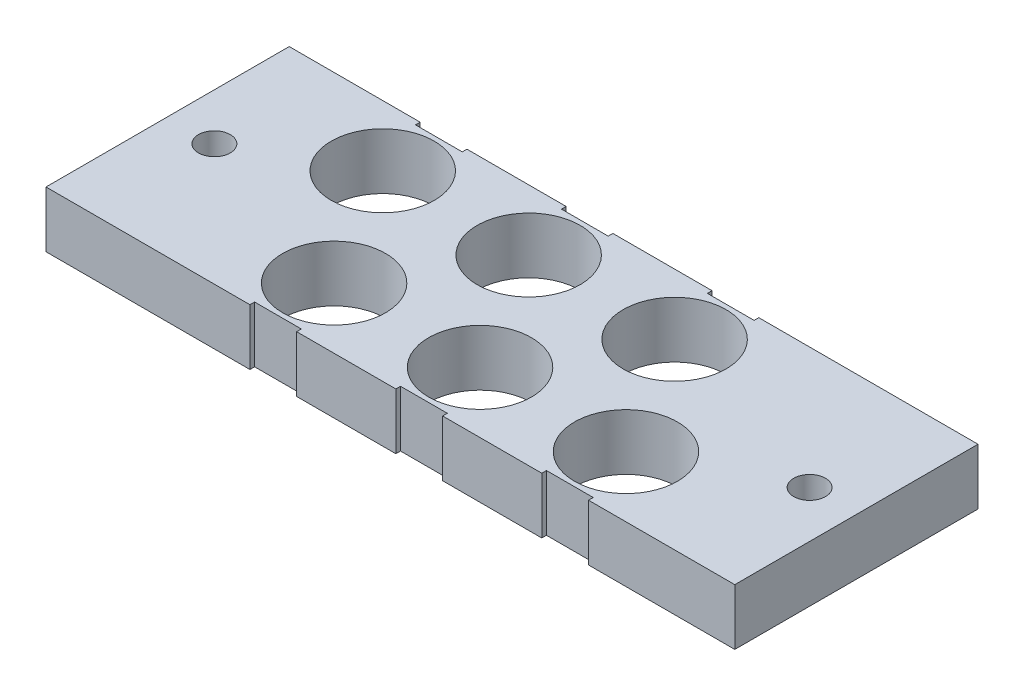
SolidWorks part; units mm, degrees
ref_plane "Front Plane" through (0, 0, 0) normal (0, 0, 1) x (1, 0, 0)
ref_plane "Top Plane" through (0, 0, 0) normal (0, 1, 0) x (1, 0, 0)
ref_plane "Right Plane" through (0, 0, 0) normal (1, 0, 0) x (0, 0, -1)
sketch "Sketch1" plane through (0, 0, 0) normal (0, 1, 0) x (1, 0, 0)
  line L0 (3.7864, -4.1649) -> (6.3864, -4.1649)
  line L1 (19.3864, -4.1649) -> (21.9864, -4.1649)
  line L2 (27.1864, -30.1649) -> (29.7864, -30.1649)
  line L3 (11.5864, -30.1649) -> (14.1864, -30.1649)
  line L4 (42.7864, -30.1649) -> (54.419, -30.1649)
  line L5 (54.419, -30.1649) -> (54.419, -4.1649)
  line L6 (54.419, -4.1649) -> (34.9864, -4.1649)
  line L7 (-9.2136, -4.1649) -> (-19.2136, -4.1649)
  line L8 (-19.2136, -4.1649) -> (-19.2136, -30.1649)
  line L9 (-19.2136, -30.1649) -> (-1.4136, -30.1649)
  line L10 (-14.2136, -4.1649) -> (-14.2136, -30.1649) construction
  line L11 (49.419, -4.1649) -> (49.419, -30.1649) construction
  circle A0 centre (-14.2136, -17.1649) radius 1.7
  circle A1 centre (49.419, -17.1649) radius 1.7
  line B0 (34.9864, -17.1649) -> (34.9864, -4.1649)
  line B1 (11.5864, -30.1649) -> (7.5864, -30.1649)
  line B2 (-0.9136, -29.6649) -> (11.0864, -29.6649)
  line B3 (11.5864, -30.1649) -> (11.5864, -17.1649)
  line B4 (27.1864, -30.1649) -> (27.1864, -17.1649)
  line B5 (42.7864, -30.1649) -> (42.7864, -17.1649)
  line B6 (-1.4136, -17.1649) -> (-1.4136, -30.1649)
  line B7 (11.0864, -29.6649) -> (11.0864, -17.6649)
  line B8 (29.7864, -17.1649) -> (29.7864, -30.1649)
  line B9 (21.9864, -4.1649) -> (21.9864, -17.1649)
  line B10 (34.4864, -16.6649) -> (34.4864, -4.6649)
  line B11 (18.8864, -16.6649) -> (18.8864, -4.6649)
  line B12 (3.7864, -17.1649) -> (3.7864, -4.1649)
  line B13 (42.2864, -29.6649) -> (42.2864, -17.6649)
  line B14 (14.6864, -29.6649) -> (26.6864, -29.6649)
  line B15 (30.2864, -17.6649) -> (30.2864, -29.6649)
  line B16 (30.2864, -17.6649) -> (42.2864, -29.6649) construction
  line B17 (14.6864, -17.6649) -> (26.6864, -29.6649) construction
  line B18 (-0.9136, -17.6649) -> (11.0864, -29.6649) construction
  line B19 (42.7864, -17.1649) -> (29.7864, -17.1649)
  line B20 (3.2864, -16.6649) -> (3.2864, -4.6649)
  line B21 (14.6864, -17.6649) -> (14.6864, -29.6649)
  line B22 (27.1864, -30.1649) -> (23.1864, -30.1649)
  line B23 (29.7864, -30.1649) -> (33.7864, -30.1649)
  line B24 (42.7864, -30.1649) -> (38.7864, -30.1649)
  line B25 (-8.7136, -10.6649) -> (3.2864, -10.6649) construction
  line B26 (6.8864, -10.6649) -> (18.8864, -10.6649) construction
  line B27 (22.4864, -10.6649) -> (34.4864, -10.6649) construction
  line B28 (-0.9136, -23.6649) -> (11.0864, -23.6649) construction
  line B29 (14.6864, -23.6649) -> (26.6864, -23.6649) construction
  line B30 (30.2864, -23.6649) -> (42.2864, -23.6649) construction
  line B31 (-27.4152, -23.6649) -> (51.2342, -23.6649) construction
  line B32 (21.9864, -17.1649) -> (34.9864, -17.1649)
  line B33 (-27.4152, -10.6649) -> (51.2342, -10.6649) construction
  line B34 (28.4864, -16.6649) -> (28.4864, -4.6649) construction
  line B35 (36.2864, -17.6649) -> (36.2864, -29.6649) construction
  line B36 (20.6864, -17.6649) -> (20.6864, -29.6649) construction
  line B37 (12.8864, -16.6649) -> (12.8864, -4.6649) construction
  line B38 (5.0864, -17.6649) -> (5.0864, -29.6649) construction
  line B39 (-2.7136, -16.6649) -> (-2.7136, -4.6649) construction
  line B40 (22.4864, -4.6649) -> (22.4864, -16.6649)
  line B41 (22.4864, -16.6649) -> (34.4864, -16.6649)
  line B42 (34.4864, -4.6649) -> (22.4864, -4.6649)
  line B43 (34.4864, -16.6649) -> (22.4864, -4.6649) construction
  line B44 (34.4864, -4.6649) -> (22.4864, -16.6649) construction
  line B45 (34.9864, -4.1649) -> (30.9864, -4.1649)
  line B46 (21.9864, -4.1649) -> (25.9864, -4.1649)
  line B47 (30.9864, -4.1649) -> (30.9864, -4.6649)
  line B48 (25.9864, -4.1649) -> (25.9864, -4.6649)
  circle B49 centre (28.4864, -10.6649) radius 5.5
  line B50 (-0.9136, -17.6649) -> (-0.9136, -29.6649)
  line B51 (11.0864, -17.6649) -> (-0.9136, -17.6649)
  line B52 (-0.9136, -29.6649) -> (11.0864, -17.6649) construction
  line B53 (11.5864, -17.1649) -> (-1.4136, -17.1649)
  line B54 (-1.4136, -30.1649) -> (2.5864, -30.1649)
  line B55 (2.5864, -30.1649) -> (2.5864, -29.6649)
  line B56 (7.5864, -30.1649) -> (7.5864, -29.6649)
  circle B57 centre (5.0864, -23.6649) radius 5.5
  line B58 (26.6864, -29.6649) -> (26.6864, -17.6649)
  line B59 (26.6864, -17.6649) -> (14.6864, -17.6649)
  line B60 (14.6864, -29.6649) -> (26.6864, -17.6649) construction
  line B61 (27.1864, -17.1649) -> (14.1864, -17.1649)
  line B62 (14.1864, -17.1649) -> (14.1864, -30.1649)
  line B63 (14.1864, -30.1649) -> (18.1864, -30.1649)
  line B64 (18.1864, -30.1649) -> (18.1864, -29.6649)
  line B65 (23.1864, -30.1649) -> (23.1864, -29.6649)
  circle B66 centre (20.6864, -23.6649) radius 5.5
  line B67 (42.2864, -17.6649) -> (30.2864, -17.6649)
  line B68 (30.2864, -29.6649) -> (42.2864, -29.6649)
  line B69 (30.2864, -29.6649) -> (42.2864, -17.6649) construction
  line B70 (33.7864, -30.1649) -> (33.7864, -29.6649)
  line B71 (38.7864, -30.1649) -> (38.7864, -29.6649)
  circle B72 centre (36.2864, -23.6649) radius 5.5
  line B73 (6.8864, -4.6649) -> (6.8864, -16.6649)
  line B74 (6.8864, -16.6649) -> (18.8864, -16.6649)
  line B75 (18.8864, -4.6649) -> (6.8864, -4.6649)
  line B76 (18.8864, -16.6649) -> (6.8864, -4.6649) construction
  line B77 (18.8864, -4.6649) -> (6.8864, -16.6649) construction
  line B78 (6.3864, -17.1649) -> (19.3864, -17.1649)
  line B79 (19.3864, -17.1649) -> (19.3864, -4.1649)
  line B80 (6.3864, -4.1649) -> (6.3864, -17.1649)
  line B81 (19.3864, -4.1649) -> (15.3864, -4.1649)
  line B82 (6.3864, -4.1649) -> (10.3864, -4.1649)
  line B83 (15.3864, -4.1649) -> (15.3864, -4.6649)
  line B84 (10.3864, -4.1649) -> (10.3864, -4.6649)
  circle B85 centre (12.8864, -10.6649) radius 5.5
  line B86 (-8.7136, -4.6649) -> (-8.7136, -16.6649)
  line B87 (-8.7136, -16.6649) -> (3.2864, -16.6649)
  line B88 (3.2864, -4.6649) -> (-8.7136, -4.6649)
  line B89 (3.2864, -16.6649) -> (-8.7136, -4.6649) construction
  line B90 (3.2864, -4.6649) -> (-8.7136, -16.6649) construction
  line B91 (-9.2136, -17.1649) -> (3.7864, -17.1649)
  line B92 (-9.2136, -4.1649) -> (-9.2136, -17.1649)
  line B93 (3.7864, -4.1649) -> (-0.2136, -4.1649)
  line B94 (-9.2136, -4.1649) -> (-5.2136, -4.1649)
  line B95 (-0.2136, -4.1649) -> (-0.2136, -4.6649)
  line B96 (-5.2136, -4.1649) -> (-5.2136, -4.6649)
  circle B97 centre (-2.7136, -10.6649) radius 5.5
  dimension "D1" = 5
  dimension "D2" = 10
  dimension "D3" = 5
sketch_block_instance "Block1-5"
sketch_block "Block1" parameters "D3"=6, "D1"=12, "D2"=12, "D4"=12, "D5"=78.6494, "D6"=78.6494, "D7"=78.6494, "D8"=10.3235, "D9"=14.0261, "D10"=17.7654, "D11"=23.7534, "D12"=22.7743, "D13"=52
sketch_block_instance "Block2-2"
sketch_block "Block2" parameters "D2"=8, "D1"=12
sketch_block_instance "Block2-3"
sketch_block_instance "Block2-4"
sketch_block_instance "Block2-5"
sketch_block_instance "Block2-6"
sketch_block_instance "Block2-7"
sketch_block_instance "Block3-1"
sketch_block "Block3"
sketch_block_instance "Block4-1"
sketch_block "Block4"
sketch_block_instance "Block5-1"
sketch_block "Block5"
sketch_block_instance "Block6-1"
sketch_block "Block6"
sketch_block_instance "Block7-1"
sketch_block "Block7"
sketch_block_instance "Block8-1"
sketch_block "Block8"
extrude "Boss-Extrude1" add sketch "Sketch1" against normal blind 6 contours B20 B88 B86 B87 B97 | B11 B75 B73 B74 B85 | B50 B2 B7 B51 B57 | B21 B14 B58 B59 B66 | B10 B42 B40 B41 B49 | B15 B68 B13 B67 B72 region at (1.5364, 0, 4.8346) region at (12.8864, 0, 4.8346) region at (0.8364, 0, 29.4952) region at (16.4364, 0, 29.4952) region at (28.4864, 0, 4.8346) region at (32.0364, 0, 29.4952)
extrude "Boss-Extrude2" add sketch "Sketch1<3>" against normal blind 6 contours B92 L7 L8 L9 B6 B91 A0 | B56 B1 B3 B53 B6 B54 B55 B2 B50 B51 B7 | B96 B94 B92 B91 B53 B12 B93 B95 B88 B20 B87 B86 | B12 B53 B80 L0 | B84 B82 B80 B53 B78 B61 B79 B81 B83 B75 B11 B74 B73 | B78 B3 L3 B62 | B79 B61 B9 L1 | B8 B32 B4 L2 | B65 B22 B4 B32 B61 B62 B63 B64 B14 B21 B59 B58 | B48 B46 B9 B32 B0 B45 B47 B42 B10 B41 B40 | B71 B24 B5 B19 B32 B8 B23 B70 B68 B15 B67 B13 | B5 L4 L5 L6 B0 B19 A1 region at (5.0864, 0, 10.6649) region at (3.6025, 0, 10.6649) region at (8.3864, 0, 4.3487) region at (5.0864, 0, 17.3487) region at (-11.6521, 0, 19.0356) region at (12.8864, 0, 23.6649) region at (16.7864, 0, 17.3487) region at (20.6864, 0, 10.6649) region at (22.1702, 0, 10.6649) region at (28.4864, 0, 23.6649) region at (32.3864, 0, 17.3487) region at (46.0882, 0, 15.4953)
sketch "Sketch1<3>" plane through (0, 0, 0) normal (0, 1, 0) x (1, 0, 0) same geometry as "Sketch1"
sketch "Sketch2" plane through (0, -6, 0) normal (0, -1, 0) x (-1, 0, 0)
  text T0 "F5"
extrude "Cut-Extrude1" cut sketch "Sketch2" against normal blind 1
